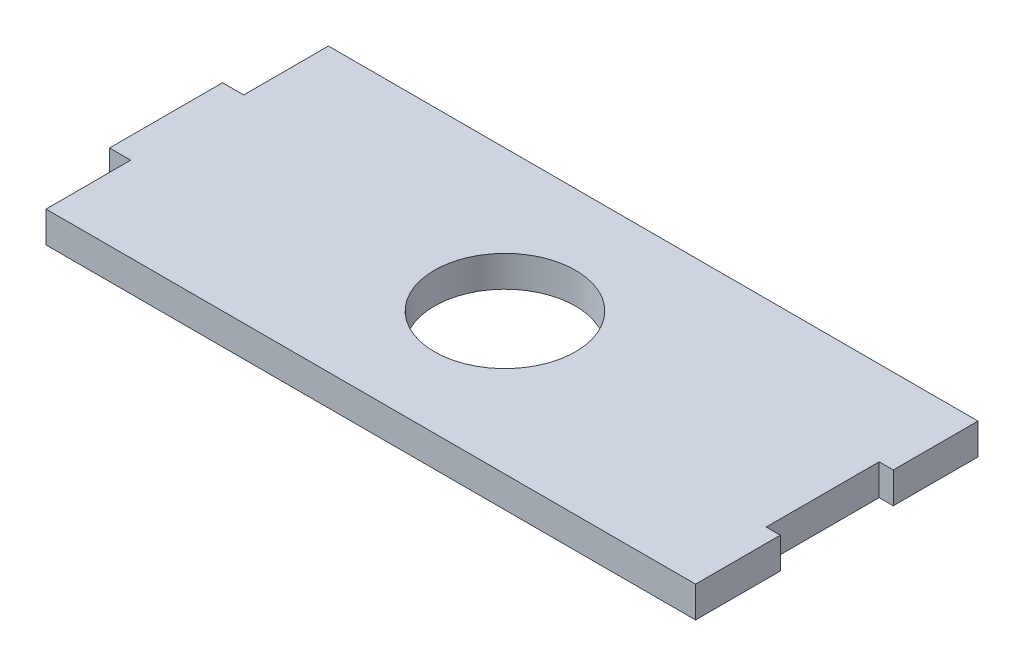
SolidWorks part; units mm, degrees
material "cardboard"
ref_plane "Front Plane" through (0, 0, 0) normal (0, 0, 1) x (1, 0, 0)
ref_plane "Top Plane" through (0, 0, 0) normal (0, 1, 0) x (1, 0, 0)
ref_plane "Right Plane" through (0, 0, 0) normal (1, 0, 0) x (0, 0, -1)
sketch "Sketch1" plane through (0, 0, 0) normal (0, 1, 0) x (1, 0, 0)
  line L0 (76.9454, 11.5977) -> (70.0953, 7.6428)
  line L1 (102.4454, -12.4023) -> (109.2956, -8.4474)
  line L2 (117.5953, 7.6428) -> (109.2956, 7.6428)
  line L3 (117.5953, -8.4474) -> (109.2956, -8.4474)
  line L4 (70.0953, 7.6428) -> (61.7956, 7.6428)
  line L5 (124.4454, 11.5977) -> (117.5953, 7.6428)
  line L6 (124.4454, -12.4023) -> (117.5953, -8.4474)
  line L7 (102.4454, 11.5977) -> (109.2956, 7.6428)
  line L8 (124.4454, 11.5977) -> (137.1954, 11.5977)
  line L9 (124.4454, -12.4023) -> (161.1954, -12.4023)
  line L10 (54.9454, 11.5977) -> (61.7956, 7.6428)
  line L11 (54.9454, -12.4023) -> (61.7956, -8.4474)
  line L12 (76.9454, -12.4023) -> (70.0953, -8.4474)
  line L13 (70.0953, -8.4474) -> (61.7956, -8.4474)
  line L14 (76.9454, 11.5977) -> (102.4454, 11.5977)
  line L15 (76.9454, -12.4023) -> (102.4454, -12.4023)
  line L16 (-12.8046, 77.3477) -> (-8.8496, 70.4976)
  line L17 (11.1954, 102.8477) -> (7.2405, 109.6979)
  line L18 (-8.8496, 117.9976) -> (-8.8496, 109.6979)
  line L19 (7.2405, 117.9976) -> (7.2405, 109.6979)
  line L20 (-8.8496, 70.4976) -> (-8.8496, 62.1979)
  line L21 (-12.8046, 124.8477) -> (-8.8496, 117.9976)
  line L22 (11.1954, 124.8477) -> (7.2405, 117.9976)
  line L23 (-12.8046, 102.8477) -> (-8.8496, 109.6979)
  line L24 (-12.8046, 124.8477) -> (-12.8046, 137.5977)
  line L25 (11.1954, 124.8477) -> (11.1954, 161.5977)
  line L26 (-12.8046, 55.3477) -> (-8.8496, 62.1979)
  line L27 (11.1954, 55.3477) -> (7.2405, 62.1979)
  line L28 (11.1954, 77.3477) -> (7.2405, 70.4976)
  line L29 (7.2405, 70.4976) -> (7.2405, 62.1979)
  line L30 (-12.8046, 77.3477) -> (-12.8046, 102.8477)
  line L31 (11.1954, 77.3477) -> (11.1954, 102.8477)
  line L32 (89.6954, 36.5977) -> (89.6954, 16.5977)
  line L33 (88.6954, 36.5977) -> (88.6954, 30.5977)
  line L34 (36.1954, 11.5977) -> (42.1954, 11.5977)
  line L35 (88.6954, 30.5977) -> (90.6954, 30.5977)
  line L36 (40.9454, 11.5977) -> (40.9454, 9.5977)
  line L37 (42.1954, 11.5977) -> (54.9454, 11.5977)
  line L38 (137.1954, 11.5977) -> (137.1954, -12.4023)
  line L39 (137.1954, 11.5977) -> (161.1954, 11.5977)
  line L40 (161.1954, 11.5977) -> (161.1954, 9.5977)
  line L41 (-29.301, 13.952) -> (-0.8046, -14.5444)
  line L42 (-29.301, 13.952) -> (-15.1588, 28.0941)
  line L43 (-0.8046, -14.5444) -> (13.3376, -0.4023)
  line L44 (-15.1588, 28.0941) -> (13.3376, -0.4023)
  line L45 (137.1954, 11.5977) -> (137.1954, 36.5977)
  line L46 (39.1954, 36.5977) -> (161.1954, 36.5977)
  line L47 (161.1954, 36.5977) -> (161.1954, 11.5977)
  line L48 (90.6954, 30.5977) -> (90.6954, 22.5977)
  line L49 (137.1954, 36.5977) -> (137.1954, 60.5977)
  line L50 (137.1954, 60.5977) -> (146.1954, 60.5977)
  line L51 (42.1954, 36.5977) -> (42.1954, 16.5977)
  line L52 (161.1954, 60.5977) -> (161.1954, 50.9197)
  line L53 (146.1954, 60.5977) -> (146.1954, 62.7977)
  line L54 (152.1954, 62.7977) -> (152.1954, 60.5977)
  line L55 (152.1954, 60.5977) -> (161.1954, 60.5977)
  line L56 (-59.8046, 137.5977) -> (-59.8046, 113.0977)
  line L57 (-39.8046, 113.0977) -> (-39.8046, 137.5977)
  line L58 (90.6954, 22.5977) -> (88.6954, 22.5977)
  line L59 (137.1954, -12.4023) -> (137.1954, -37.4023)
  line L60 (146.1954, -37.4023) -> (152.1954, -37.4023)
  line L61 (161.1954, -37.4023) -> (161.1954, -12.4023)
  line L62 (42.1954, -37.4023) -> (42.1954, -17.4023)
  line L63 (137.1954, -37.4023) -> (137.1954, -38.5823)
  line L64 (152.1954, -38.5823) -> (161.1954, -38.5823)
  line L65 (161.1954, -38.5823) -> (161.1954, -37.4023)
  line L66 (146.1954, -38.5823) -> (146.1954, -37.4023)
  line L67 (152.1954, -38.5823) -> (152.1954, -37.4023)
  line L68 (-38.9846, -138.4023) -> (-38.9846, -147.4023)
  line L69 (88.6954, 22.5977) -> (88.6954, 16.5977)
  line L70 (88.6954, 11.5977) -> (88.6954, 3.5977)
  line L71 (42.1954, -12.4023) -> (54.9454, -12.4023)
  line L72 (36.1954, -12.4023) -> (42.1954, -12.4023)
  line L73 (89.6692, 11.5977) -> (89.6692, -12.4023)
  line L74 (88.6954, 3.5977) -> (90.6954, 3.5977)
  line L75 (90.6954, 3.5977) -> (90.6954, -4.4023)
  line L76 (90.6954, -4.4023) -> (88.6954, -4.4023)
  line L77 (135.1954, 11.5977) -> (135.1954, 3.5977)
  line L78 (135.1954, 3.5977) -> (139.1954, 3.5977)
  line L79 (37.3754, 161.5977) -> (37.3754, 152.5977)
  line L80 (37.1954, 34.5977) -> (37.1954, 18.5977)
  line L81 (39.1954, 16.5977) -> (137.1954, 16.5977)
  line L82 (40.9454, 23.5977) -> (40.9454, 16.5977)
  line L83 (42.1954, 29.5977) -> (39.1954, 29.5977)
  line L84 (39.1954, 29.5977) -> (39.1954, 23.5977)
  line L85 (43.4454, 5.5977) -> (40.9454, 5.5977)
  line L86 (5.1954, -42.1523) -> (5.1954, -40.1523)
  line L87 (40.9454, -6.4023) -> (43.4454, -6.4023)
  line L88 (43.4454, 5.5977) -> (43.4454, -6.4023)
  line L89 (42.1954, 11.5977) -> (42.1954, 5.5977)
  line L90 (40.9454, 9.5977) -> (43.4454, 9.5977)
  line L91 (43.4454, 9.5977) -> (43.4454, 7.5977)
  line L92 (43.4454, 7.5977) -> (40.9454, 7.5977)
  line L93 (40.9454, 7.5977) -> (40.9454, 5.5977)
  line L94 (40.9454, -8.4023) -> (40.9454, -6.4023)
  line L95 (43.4454, -8.4023) -> (40.9454, -8.4023)
  line L96 (43.4454, -10.4023) -> (43.4454, -8.4023)
  line L97 (40.9454, -10.4023) -> (43.4454, -10.4023)
  line L98 (40.9454, -12.4023) -> (40.9454, -10.4023)
  line L99 (139.1954, 3.5977) -> (139.1954, -4.4023)
  line L100 (139.1954, -4.4023) -> (135.1954, -4.4023)
  line L101 (135.1954, -4.4023) -> (135.1954, -12.4023)
  line L102 (137.1954, 13.5977) -> (145.1954, 13.5977)
  line L103 (145.1954, 13.5977) -> (145.1954, 9.5977)
  line L104 (145.1954, 9.5977) -> (153.1954, 9.5977)
  line L105 (153.1954, 9.5977) -> (153.1954, 13.5977)
  line L106 (153.1954, 13.5977) -> (161.1954, 13.5977)
  line L107 (135.6954, 36.5977) -> (135.6954, 30.5977)
  line L108 (135.6954, 30.5977) -> (138.6954, 30.5977)
  line L109 (138.6954, 30.5977) -> (138.6954, 22.5977)
  line L110 (138.6954, 22.5977) -> (135.6954, 22.5977)
  line L111 (135.6954, 22.5977) -> (135.6954, 16.5977)
  line L112 (88.6954, -4.4023) -> (88.6954, -12.4023)
  line L113 (88.6954, -23.4023) -> (88.6954, -17.4023)
  line L114 (89.6954, -37.4023) -> (89.6954, -17.4023)
  line L115 (90.6954, -23.4023) -> (88.6954, -23.4023)
  line L116 (90.6954, -31.4023) -> (90.6954, -23.4023)
  line L117 (153.1954, -14.4023) -> (161.1954, -14.4023)
  line L118 (153.1954, -10.4023) -> (153.1954, -14.4023)
  line L119 (145.1954, -10.4023) -> (153.1954, -10.4023)
  line L120 (145.1954, -14.4023) -> (145.1954, -10.4023)
  line L121 (137.1954, -14.4023) -> (145.1954, -14.4023)
  line L122 (135.6954, -23.4023) -> (135.6954, -17.4023)
  line L123 (138.6954, -23.4023) -> (135.6954, -23.4023)
  line L124 (40.9454, 36.5977) -> (40.9454, 29.5977)
  line L125 (42.1954, 23.5977) -> (39.1954, 23.5977)
  line L126 (137.1954, -37.4023) -> (39.1954, -37.4023)
  line L127 (37.1954, -35.4023) -> (37.1954, -19.4023)
  line L128 (39.1954, -17.4023) -> (137.1954, -17.4023)
  line L129 (138.6954, -31.4023) -> (138.6954, -23.4023)
  line L130 (135.6954, -31.4023) -> (138.6954, -31.4023)
  line L131 (135.6954, -37.4023) -> (135.6954, -31.4023)
  line L132 (88.6954, -31.4023) -> (90.6954, -31.4023)
  line L133 (88.6954, -37.4023) -> (88.6954, -31.4023)
  line L134 (137.1954, 38.5977) -> (145.1954, 38.5977)
  line L135 (145.1954, 38.5977) -> (145.1954, 34.5977)
  line L136 (145.1954, 34.5977) -> (153.1954, 34.5977)
  line L137 (153.1954, 34.5977) -> (153.1954, 38.5977)
  line L138 (153.1954, 38.5977) -> (161.1954, 38.5977)
  line L139 (-45.3046, 133.3477) -> (-45.3046, 117.3477)
  line L140 (-56.8046, 133.3477) -> (-54.3046, 133.3477)
  line L141 (-56.8046, 133.3477) -> (-56.8046, 117.3477)
  line L142 (-56.8046, 117.3477) -> (-54.3046, 117.3477)
  line L143 (-54.3046, 133.3477) -> (-54.3046, 117.3477)
  line L144 (40.9454, -24.4023) -> (40.9454, -17.4023)
  line L145 (42.1954, -24.4023) -> (39.1954, -24.4023)
  line L146 (39.1954, -30.4023) -> (39.1954, -24.4023)
  line L147 (42.1954, -30.4023) -> (39.1954, -30.4023)
  line L148 (40.9454, -37.4023) -> (40.9454, -30.4023)
  line L149 (196.1954, 4.5977) -> (196.1954, -5.4023)
  line L150 (191.1954, 9.5977) -> (161.1954, 9.5977)
  line L151 (191.1954, -10.4023) -> (161.1954, -10.4023)
  line L152 (191.1954, 9.5977) -> (196.1954, 4.5977)
  line L153 (196.1954, -5.4023) -> (191.1954, -10.4023)
  line L154 (161.1954, -10.4023) -> (161.1954, -12.4023)
  line L155 (137.1954, 62.7977) -> (146.1954, 62.7977)
  line L156 (137.1954, 62.7977) -> (137.1954, 64.7977)
  line L157 (137.1954, 64.7977) -> (161.1954, 64.7977)
  line L158 (161.1954, 64.7977) -> (161.1954, 62.7977)
  line L159 (152.1954, 62.7977) -> (161.1954, 62.7977)
  line L160 (-42.8046, 117.3477) -> (-45.3046, 117.3477)
  line L161 (-42.8046, 133.3477) -> (-42.8046, 117.3477)
  line L162 (-42.8046, 133.3477) -> (-45.3046, 133.3477)
  line L163 (154.5954, 50.9197) -> (161.1954, 50.9197)
  line L164 (154.5954, 50.9197) -> (154.5954, 46.4197)
  line L165 (154.5954, 46.4197) -> (161.1954, 46.4197)
  line L166 (161.1954, 46.4197) -> (161.1954, 36.5977)
  line L167 (11.1954, -78.1523) -> (7.2405, -71.3021)
  line L168 (-12.8046, -103.6523) -> (-8.8496, -110.5024)
  line L169 (7.2405, -118.8021) -> (7.2405, -110.5024)
  line L170 (11.1954, -37.4023) -> (11.1954, -43.4023)
  line L171 (11.1954, -42.1523) -> (9.1954, -42.1523)
  line L172 (11.1954, -43.4023) -> (11.1954, -56.1523)
  line L173 (-8.8496, -118.8021) -> (-8.8496, -110.5024)
  line L174 (7.2405, -71.3021) -> (7.2405, -63.0024)
  line L175 (11.1954, -125.6523) -> (7.2405, -118.8021)
  line L176 (-12.8046, -125.6523) -> (-8.8496, -118.8021)
  line L177 (11.1954, -103.6523) -> (7.2405, -110.5024)
  line L178 (11.1954, -125.6523) -> (11.1954, -138.4023)
  line L179 (-12.8046, -125.6523) -> (-12.8046, -162.4023)
  line L180 (11.1954, -56.1523) -> (7.2405, -63.0024)
  line L181 (-12.8046, -56.1523) -> (-8.8496, -63.0024)
  line L182 (36.1954, -43.4023) -> (16.1954, -43.4023)
  line L183 (-12.8046, -78.1523) -> (-8.8496, -71.3021)
  line L184 (-8.8496, -71.3021) -> (-8.8496, -63.0024)
  line L185 (11.1954, -78.1523) -> (11.1954, -103.6523)
  line L186 (-12.8046, -78.1523) -> (-12.8046, -103.6523)
  line L187 (36.1954, -90.9023) -> (16.1954, -90.9023)
  line L188 (36.1954, -89.9023) -> (30.1954, -89.9023)
  line L189 (30.1954, -89.9023) -> (30.1954, -91.9023)
  line L190 (11.1954, -138.4023) -> (-12.8046, -138.4023)
  line L191 (11.1954, -138.4023) -> (11.1954, -162.4023)
  line L192 (11.1954, -162.4023) -> (9.1954, -162.4023)
  line L193 (11.1954, -138.4023) -> (36.1954, -138.4023)
  line L194 (36.1954, -40.4023) -> (36.1954, -162.4023)
  line L195 (-37.8046, -43.4023) -> (-17.8046, -43.4023)
  line L196 (36.1954, -162.4023) -> (11.1954, -162.4023)
  line L197 (30.1954, -91.9023) -> (22.1954, -91.9023)
  line L198 (36.1954, -138.4023) -> (60.1954, -138.4023)
  line L199 (60.1954, -138.4023) -> (60.1954, -147.4023)
  line L200 (60.1954, -162.4023) -> (50.5174, -162.4023)
  line L201 (60.1954, -147.4023) -> (62.3954, -147.4023)
  line L202 (62.3954, -153.4023) -> (60.1954, -153.4023)
  line L203 (60.1954, -153.4023) -> (60.1954, -162.4023)
  line L204 (-12.8046, -43.4023) -> (-12.8046, -56.1523)
  line L205 (-12.8046, -37.4023) -> (-12.8046, -43.4023)
  line L206 (22.1954, -91.9023) -> (22.1954, -89.9023)
  line L207 (-12.8046, -138.4023) -> (-37.8046, -138.4023)
  line L208 (-37.8046, -147.4023) -> (-37.8046, -153.4023)
  line L209 (37.3754, 146.5977) -> (37.3754, 137.5977)
  line L210 (34.1954, -38.4023) -> (18.1954, -38.4023)
  line L211 (16.1954, -40.4023) -> (16.1954, -138.4023)
  line L212 (23.1954, -42.1523) -> (16.1954, -42.1523)
  line L213 (29.1954, -43.4023) -> (29.1954, -40.4023)
  line L214 (29.1954, -40.4023) -> (23.1954, -40.4023)
  line L215 (5.1954, -44.6523) -> (5.1954, -42.1523)
  line L216 (-37.8046, -162.4023) -> (-12.8046, -162.4023)
  line L217 (-6.8046, -42.1523) -> (-6.8046, -44.6523)
  line L218 (5.1954, -44.6523) -> (-6.8046, -44.6523)
  line L219 (11.1954, -43.4023) -> (5.1954, -43.4023)
  line L220 (9.1954, -42.1523) -> (9.1954, -44.6523)
  line L221 (9.1954, -44.6523) -> (7.1954, -44.6523)
  line L222 (7.1954, -44.6523) -> (7.1954, -42.1523)
  line L223 (7.1954, -42.1523) -> (5.1954, -42.1523)
  line L224 (-8.8046, -42.1523) -> (-6.8046, -42.1523)
  line L225 (-8.8046, -44.6523) -> (-8.8046, -42.1523)
  line L226 (-10.8046, -44.6523) -> (-8.8046, -44.6523)
  line L227 (-10.8046, -42.1523) -> (-10.8046, -44.6523)
  line L228 (-12.8046, -42.1523) -> (-10.8046, -42.1523)
  line L229 (-37.8046, -138.4023) -> (-38.9846, -138.4023)
  line L230 (-38.9846, -153.4023) -> (-38.9846, -162.4023)
  line L231 (-38.9846, -162.4023) -> (-37.8046, -162.4023)
  line L232 (-38.9846, -147.4023) -> (-37.8046, -147.4023)
  line L233 (-38.9846, -153.4023) -> (-37.8046, -153.4023)
  line L234 (-162.8046, 37.7777) -> (-153.8046, 37.7777)
  line L235 (22.1954, -89.9023) -> (16.1954, -89.9023)
  line L236 (11.1954, -89.9023) -> (3.1954, -89.9023)
  line L237 (11.1954, -90.8761) -> (-12.8046, -90.8761)
  line L238 (3.1954, -89.9023) -> (3.1954, -91.9023)
  line L239 (3.1954, -91.9023) -> (-4.8046, -91.9023)
  line L240 (-4.8046, -91.9023) -> (-4.8046, -89.9023)
  line L241 (11.1954, -136.4023) -> (3.1954, -136.4023)
  line L242 (3.1954, -136.4023) -> (3.1954, -140.4023)
  line L243 (3.1954, -140.4023) -> (-4.8046, -140.4023)
  line L244 (-4.8046, -140.4023) -> (-4.8046, -136.4023)
  line L245 (-4.8046, -136.4023) -> (-12.8046, -136.4023)
  line L246 (13.1954, -138.4023) -> (13.1954, -146.4023)
  line L247 (13.1954, -146.4023) -> (9.1954, -146.4023)
  line L248 (9.1954, -146.4023) -> (9.1954, -154.4023)
  line L249 (9.1954, -154.4023) -> (13.1954, -154.4023)
  line L250 (13.1954, -154.4023) -> (13.1954, -162.4023)
  line L251 (36.1954, -136.9023) -> (30.1954, -136.9023)
  line L252 (30.1954, -136.9023) -> (30.1954, -139.9023)
  line L253 (30.1954, -139.9023) -> (22.1954, -139.9023)
  line L254 (36.1954, -42.1523) -> (29.1954, -42.1523)
  line L255 (23.1954, -43.4023) -> (23.1954, -40.4023)
  line L256 (-37.8046, -138.4023) -> (-37.8046, -40.4023)
  line L257 (-35.8046, -38.4023) -> (-19.8046, -38.4023)
  line L258 (-17.8046, -40.4023) -> (-17.8046, -138.4023)
  line L259 (22.1954, -139.9023) -> (22.1954, -136.9023)
  line L260 (22.1954, -136.9023) -> (16.1954, -136.9023)
  line L261 (-4.8046, -89.9023) -> (-12.8046, -89.9023)
  line L262 (-23.8046, -89.9023) -> (-17.8046, -89.9023)
  line L263 (-37.8046, -90.9023) -> (-17.8046, -90.9023)
  line L264 (-23.8046, -91.9023) -> (-23.8046, -89.9023)
  line L265 (-31.8046, -91.9023) -> (-23.8046, -91.9023)
  line L266 (-14.8046, -154.4023) -> (-14.8046, -162.4023)
  line L267 (-10.8046, -154.4023) -> (-14.8046, -154.4023)
  line L268 (-10.8046, -146.4023) -> (-10.8046, -154.4023)
  line L269 (-14.8046, -146.4023) -> (-10.8046, -146.4023)
  line L270 (-14.8046, -138.4023) -> (-14.8046, -146.4023)
  line L271 (-23.8046, -136.9023) -> (-17.8046, -136.9023)
  line L272 (-23.8046, -139.9023) -> (-23.8046, -136.9023)
  line L273 (-31.8046, -139.9023) -> (-23.8046, -139.9023)
  line L274 (-24.8046, -42.1523) -> (-17.8046, -42.1523)
  line L275 (-24.8046, -43.4023) -> (-24.8046, -40.4023)
  line L276 (-30.8046, -40.4023) -> (-24.8046, -40.4023)
  line L277 (-30.8046, -43.4023) -> (-30.8046, -40.4023)
  line L278 (-37.8046, -42.1523) -> (-30.8046, -42.1523)
  line L279 (-31.8046, -136.9023) -> (-31.8046, -139.9023)
  line L280 (-37.8046, -136.9023) -> (-31.8046, -136.9023)
  line L281 (-31.8046, -89.9023) -> (-31.8046, -91.9023)
  line L282 (-37.8046, -89.9023) -> (-31.8046, -89.9023)
  line L283 (38.1954, -138.4023) -> (38.1954, -146.4023)
  line L284 (38.1954, -146.4023) -> (34.1954, -146.4023)
  line L285 (34.1954, -146.4023) -> (34.1954, -154.4023)
  line L286 (34.1954, -154.4023) -> (38.1954, -154.4023)
  line L287 (38.1954, -154.4023) -> (38.1954, -162.4023)
  line L288 (4.1954, -197.4023) -> (-5.8046, -197.4023)
  line L289 (9.1954, -192.4023) -> (9.1954, -162.4023)
  line L290 (-10.8046, -192.4023) -> (-10.8046, -162.4023)
  line L291 (9.1954, -192.4023) -> (4.1954, -197.4023)
  line L292 (-5.8046, -197.4023) -> (-10.8046, -192.4023)
  line L293 (-10.8046, -162.4023) -> (-12.8046, -162.4023)
  line L294 (62.3954, -138.4023) -> (62.3954, -147.4023)
  line L295 (62.3954, -138.4023) -> (64.3954, -138.4023)
  line L296 (64.3954, -138.4023) -> (64.3954, -162.4023)
  line L297 (64.3954, -162.4023) -> (62.3954, -162.4023)
  line L298 (62.3954, -153.4023) -> (62.3954, -162.4023)
  line L299 (-37.8046, -12.4023) -> (-43.8046, -12.4023)
  line L300 (-42.5546, -12.4023) -> (-42.5546, -10.4023)
  line L301 (-43.8046, -12.4023) -> (-56.5546, -12.4023)
  line L302 (50.5174, -155.8023) -> (50.5174, -162.4023)
  line L303 (50.5174, -155.8023) -> (46.0174, -155.8023)
  line L304 (-43.8046, -37.4023) -> (-43.8046, -17.4023)
  line L305 (46.0174, -155.8023) -> (46.0174, -162.4023)
  line L306 (46.0174, -162.4023) -> (36.1954, -162.4023)
  line L307 (-78.5546, -12.4023) -> (-71.7044, -8.4474)
  line L308 (-104.0546, 11.5977) -> (-110.9047, 7.6428)
  line L309 (-119.2044, -8.4474) -> (-110.9047, -8.4474)
  line L310 (-119.2044, 7.6428) -> (-110.9047, 7.6428)
  line L311 (-71.7044, -8.4474) -> (-63.4047, -8.4474)
  line L312 (-126.0546, -12.4023) -> (-119.2044, -8.4474)
  line L313 (-126.0546, 11.5977) -> (-119.2044, 7.6428)
  line L314 (-104.0546, -12.4023) -> (-110.9047, -8.4474)
  line L315 (-126.0546, -12.4023) -> (-138.8046, -12.4023)
  line L316 (-43.8046, 36.5977) -> (-43.8046, 16.5977)
  line L317 (-126.0546, 11.5977) -> (-162.8046, 11.5977)
  line L318 (-56.5546, -12.4023) -> (-63.4047, -8.4474)
  line L319 (-56.5546, 11.5977) -> (-63.4047, 7.6428)
  line L320 (-78.5546, 11.5977) -> (-71.7044, 7.6428)
  line L321 (-71.7044, 7.6428) -> (-63.4047, 7.6428)
  line L322 (-78.5546, -12.4023) -> (-104.0546, -12.4023)
  line L323 (-78.5546, 11.5977) -> (-104.0546, 11.5977)
  line L324 (-91.3046, -37.4023) -> (-91.3046, -17.4023)
  line L325 (-43.8046, 11.5977) -> (-56.5546, 11.5977)
  line L326 (-37.8046, 11.5977) -> (-43.8046, 11.5977)
  line L327 (-90.3046, -37.4023) -> (-90.3046, -31.4023)
  line L328 (-90.3046, -31.4023) -> (-92.3046, -31.4023)
  line L329 (-138.8046, -12.4023) -> (-138.8046, 11.5977)
  line L330 (-138.8046, -12.4023) -> (-162.8046, -12.4023)
  line L331 (-162.8046, -12.4023) -> (-162.8046, -10.4023)
  line L332 (-138.8046, -12.4023) -> (-138.8046, -37.4023)
  line L333 (137.1954, -38.5823) -> (146.1954, -38.5823)
  line L334 (-38.8046, -35.4023) -> (-38.8046, -19.4023)
  line L335 (-40.8046, -17.4023) -> (-138.8046, -17.4023)
  line L336 (-42.5546, -24.4023) -> (-42.5546, -17.4023)
  line L337 (-43.8046, -30.4023) -> (-40.8046, -30.4023)
  line L338 (-40.8046, -30.4023) -> (-40.8046, -24.4023)
  line L339 (-45.0546, -6.4023) -> (-42.5546, -6.4023)
  line L340 (-40.8046, -37.4023) -> (-162.8046, -37.4023)
  line L341 (-42.5546, 5.5977) -> (-45.0546, 5.5977)
  line L342 (-45.0546, -6.4023) -> (-45.0546, 5.5977)
  line L343 (-43.8046, -12.4023) -> (-43.8046, -6.4023)
  line L344 (-42.5546, -10.4023) -> (-45.0546, -10.4023)
  line L345 (-45.0546, -10.4023) -> (-45.0546, -8.4023)
  line L346 (-45.0546, -8.4023) -> (-42.5546, -8.4023)
  line L347 (-42.5546, -8.4023) -> (-42.5546, -6.4023)
  line L348 (-42.5546, 7.5977) -> (-42.5546, 5.5977)
  line L349 (-45.0546, 7.5977) -> (-42.5546, 7.5977)
  line L350 (-45.0546, 9.5977) -> (-45.0546, 7.5977)
  line L351 (-42.5546, 9.5977) -> (-45.0546, 9.5977)
  line L352 (-42.5546, 11.5977) -> (-42.5546, 9.5977)
  line L353 (-162.8046, -37.4023) -> (-162.8046, -12.4023)
  line L354 (-92.3046, -31.4023) -> (-92.3046, -23.4023)
  line L355 (-138.8046, -37.4023) -> (-138.8046, -61.4023)
  line L356 (-138.8046, -61.4023) -> (-147.8046, -61.4023)
  line L357 (-162.8046, -61.4023) -> (-162.8046, -51.7243)
  line L358 (-147.8046, -61.4023) -> (-147.8046, -63.6023)
  line L359 (-153.8046, -63.6023) -> (-153.8046, -61.4023)
  line L360 (-153.8046, -61.4023) -> (-162.8046, -61.4023)
  line L361 (-92.3046, -23.4023) -> (-90.3046, -23.4023)
  line L362 (-138.8046, 11.5977) -> (-138.8046, 36.5977)
  line L363 (-147.8046, 36.5977) -> (-153.8046, 36.5977)
  line L364 (-162.8046, 36.5977) -> (-162.8046, 11.5977)
  line L365 (-138.8046, 36.5977) -> (-138.8046, 37.7777)
  line L366 (-162.8046, 37.7777) -> (-162.8046, 36.5977)
  line L367 (-147.8046, 37.7777) -> (-147.8046, 36.5977)
  line L368 (-153.8046, 37.7777) -> (-153.8046, 36.5977)
  line L369 (-147.8046, 37.7777) -> (-138.8046, 37.7777)
  line L370 (-90.3046, -23.4023) -> (-90.3046, -17.4023)
  line L371 (-90.3046, -12.4023) -> (-90.3046, -4.4023)
  line L372 (-91.2784, -12.4023) -> (-91.2784, 11.5977)
  line L373 (-90.3046, -4.4023) -> (-92.3046, -4.4023)
  line L374 (-42.5546, -37.4023) -> (-42.5546, -30.4023)
  line L375 (-43.8046, -24.4023) -> (-40.8046, -24.4023)
  line L376 (-138.8046, 36.5977) -> (-40.8046, 36.5977)
  line L377 (-38.8046, 34.5977) -> (-38.8046, 18.5977)
  line L378 (-40.8046, 16.5977) -> (-138.8046, 16.5977)
  line L379 (-92.3046, -4.4023) -> (-92.3046, 3.5977)
  line L380 (-92.3046, 3.5977) -> (-90.3046, 3.5977)
  line L381 (-136.8046, -12.4023) -> (-136.8046, -4.4023)
  line L382 (-136.8046, -4.4023) -> (-140.8046, -4.4023)
  line L383 (-140.8046, -4.4023) -> (-140.8046, 3.5977)
  line L384 (-140.8046, 3.5977) -> (-136.8046, 3.5977)
  line L385 (-136.8046, 3.5977) -> (-136.8046, 11.5977)
  line L386 (-138.8046, -14.4023) -> (-146.8046, -14.4023)
  line L387 (-146.8046, -14.4023) -> (-146.8046, -10.4023)
  line L388 (-146.8046, -10.4023) -> (-154.8046, -10.4023)
  line L389 (-154.8046, -10.4023) -> (-154.8046, -14.4023)
  line L390 (-154.8046, -14.4023) -> (-162.8046, -14.4023)
  line L391 (-137.3046, -37.4023) -> (-137.3046, -31.4023)
  line L392 (-37.8046, 90.0977) -> (-17.8046, 90.0977)
  line L393 (-37.8046, 89.0977) -> (-31.8046, 89.0977)
  line L394 (-42.5546, 23.5977) -> (-42.5546, 16.5977)
  line L395 (-43.8046, 23.5977) -> (-40.8046, 23.5977)
  line L396 (-40.8046, 29.5977) -> (-40.8046, 23.5977)
  line L397 (-43.8046, 29.5977) -> (-40.8046, 29.5977)
  line L398 (-42.5546, 36.5977) -> (-42.5546, 29.5977)
  line L399 (-137.3046, -31.4023) -> (-140.3046, -31.4023)
  line L400 (-140.3046, -31.4023) -> (-140.3046, -23.4023)
  line L401 (-140.3046, -23.4023) -> (-137.3046, -23.4023)
  line L402 (-137.3046, -23.4023) -> (-137.3046, -17.4023)
  line L403 (-90.3046, 3.5977) -> (-90.3046, 11.5977)
  line L404 (-90.3046, 22.5977) -> (-90.3046, 16.5977)
  line L405 (-91.3046, 36.5977) -> (-91.3046, 16.5977)
  line L406 (-92.3046, 22.5977) -> (-90.3046, 22.5977)
  line L407 (-92.3046, 30.5977) -> (-92.3046, 22.5977)
  line L408 (-154.8046, 13.5977) -> (-162.8046, 13.5977)
  line L409 (-154.8046, 9.5977) -> (-154.8046, 13.5977)
  line L410 (-146.8046, 9.5977) -> (-154.8046, 9.5977)
  line L411 (-146.8046, 13.5977) -> (-146.8046, 9.5977)
  line L412 (-138.8046, 13.5977) -> (-146.8046, 13.5977)
  line L413 (-137.3046, 22.5977) -> (-137.3046, 16.5977)
  line L414 (-140.3046, 22.5977) -> (-137.3046, 22.5977)
  line L415 (-140.3046, 30.5977) -> (-140.3046, 22.5977)
  line L416 (-137.3046, 30.5977) -> (-140.3046, 30.5977)
  line L417 (-137.3046, 36.5977) -> (-137.3046, 30.5977)
  line L418 (-90.3046, 30.5977) -> (-92.3046, 30.5977)
  line L419 (-90.3046, 36.5977) -> (-90.3046, 30.5977)
  line L420 (-138.8046, -39.4023) -> (-146.8046, -39.4023)
  line L421 (-146.8046, -39.4023) -> (-146.8046, -35.4023)
  line L422 (-146.8046, -35.4023) -> (-154.8046, -35.4023)
  line L423 (-154.8046, -35.4023) -> (-154.8046, -39.4023)
  line L424 (-154.8046, -39.4023) -> (-162.8046, -39.4023)
  line L425 (-12.8046, 41.3477) -> (-10.8046, 41.3477)
  line L426 (-31.8046, 89.0977) -> (-31.8046, 91.0977)
  line L427 (-12.8046, 137.5977) -> (11.1954, 137.5977)
  line L428 (-12.8046, 137.5977) -> (-12.8046, 161.5977)
  line L429 (-12.8046, 161.5977) -> (-10.8046, 161.5977)
  line L430 (-12.8046, 137.5977) -> (-37.8046, 137.5977)
  line L431 (-37.8046, 137.5977) -> (-37.8046, 161.5977)
  line L432 (-37.8046, 161.5977) -> (-12.8046, 161.5977)
  line L433 (-37.8046, 137.5977) -> (-37.8046, 42.5977)
  line L434 (-37.8046, 42.5977) -> (-17.8046, 42.5977)
  line L435 (-17.8046, 42.5977) -> (-17.8046, 137.5977)
  line L436 (-31.8046, 91.0977) -> (-23.8046, 91.0977)
  line L437 (-37.8046, 137.5977) -> (-61.8046, 137.5977)
  line L438 (-61.8046, 137.5977) -> (-61.8046, 146.5977)
  line L439 (-61.8046, 161.5977) -> (-52.1265, 161.5977)
  line L440 (-61.8046, 146.5977) -> (-64.0046, 146.5977)
  line L441 (-64.0046, 152.5977) -> (-61.8046, 152.5977)
  line L442 (-61.8046, 152.5977) -> (-61.8046, 161.5977)
  line L443 (-59.8046, 113.0977) -> (-39.8046, 113.0977)
  line L444 (36.1954, 42.5977) -> (16.1954, 42.5977)
  line L445 (-23.8046, 91.0977) -> (-23.8046, 89.0977)
  line L446 (36.1954, 137.5977) -> (36.1954, 42.5977)
  line L447 (16.1954, 42.5977) -> (16.1954, 137.5977)
  line L448 (11.1954, 137.5977) -> (36.1954, 137.5977)
  line L449 (36.1954, 146.5977) -> (36.1954, 152.5977)
  line L450 (36.1954, 161.5977) -> (11.1954, 161.5977)
  line L451 (11.1954, 36.5977) -> (11.1954, 55.3477)
  line L452 (36.1954, 137.5977) -> (37.3754, 137.5977)
  line L453 (37.3754, 161.5977) -> (36.1954, 161.5977)
  line L454 (37.3754, 146.5977) -> (36.1954, 146.5977)
  line L455 (37.3754, 152.5977) -> (36.1954, 152.5977)
  line L456 (-37.8046, 42.5977) -> (-37.8046, 39.5977)
  line L457 (-35.8046, 37.5977) -> (-19.8046, 37.5977)
  line L458 (-17.8046, 39.5977) -> (-17.8046, 42.5977)
  line L459 (34.1954, 37.5977) -> (18.1954, 37.5977)
  line L460 (16.1954, 39.5977) -> (16.1954, 42.5977)
  line L461 (-6.8046, 43.8477) -> (-6.8046, 41.3477)
  line L462 (-23.8046, 89.0977) -> (-17.8046, 89.0977)
  line L463 (5.1954, 41.3477) -> (5.1954, 43.8477)
  line L464 (-6.8046, 43.8477) -> (5.1954, 43.8477)
  line L465 (-12.8046, 42.5977) -> (-6.8046, 42.5977)
  line L466 (-10.8046, 41.3477) -> (-10.8046, 43.8477)
  line L467 (-10.8046, 43.8477) -> (-8.8046, 43.8477)
  line L468 (-8.8046, 43.8477) -> (-8.8046, 41.3477)
  line L469 (-8.8046, 41.3477) -> (-6.8046, 41.3477)
  line L470 (7.1954, 41.3477) -> (5.1954, 41.3477)
  line L471 (7.1954, 43.8477) -> (7.1954, 41.3477)
  line L472 (9.1954, 43.8477) -> (7.1954, 43.8477)
  line L473 (9.1954, 41.3477) -> (9.1954, 43.8477)
  line L474 (11.1954, 41.3477) -> (9.1954, 41.3477)
  line L475 (-12.8046, 89.0977) -> (-4.8046, 89.0977)
  line L476 (-12.8046, 90.0715) -> (11.1954, 90.0715)
  line L477 (-4.8046, 89.0977) -> (-4.8046, 91.0977)
  line L478 (-4.8046, 91.0977) -> (3.1954, 91.0977)
  line L479 (3.1954, 91.0977) -> (3.1954, 89.0977)
  line L480 (-12.8046, 135.5977) -> (-4.8046, 135.5977)
  line L481 (-4.8046, 135.5977) -> (-4.8046, 139.5977)
  line L482 (-4.8046, 139.5977) -> (3.1954, 139.5977)
  line L483 (3.1954, 139.5977) -> (3.1954, 135.5977)
  line L484 (3.1954, 135.5977) -> (11.1954, 135.5977)
  line L485 (-14.8046, 137.5977) -> (-14.8046, 145.5977)
  line L486 (-14.8046, 145.5977) -> (-10.8046, 145.5977)
  line L487 (-10.8046, 145.5977) -> (-10.8046, 153.5977)
  line L488 (-10.8046, 153.5977) -> (-14.8046, 153.5977)
  line L489 (-14.8046, 153.5977) -> (-14.8046, 161.5977)
  line L490 (-37.8046, 136.0977) -> (-31.8046, 136.0977)
  line L491 (-31.8046, 136.0977) -> (-31.8046, 139.0977)
  line L492 (-31.8046, 139.0977) -> (-23.8046, 139.0977)
  line L493 (-23.8046, 139.0977) -> (-23.8046, 136.0977)
  line L494 (-23.8046, 136.0977) -> (-17.8046, 136.0977)
  line L495 (3.1954, 89.0977) -> (11.1954, 89.0977)
  line L496 (22.1954, 89.0977) -> (16.1954, 89.0977)
  line L497 (36.1954, 90.0977) -> (16.1954, 90.0977)
  line L498 (22.1954, 91.0977) -> (22.1954, 89.0977)
  line L499 (30.1954, 91.0977) -> (22.1954, 91.0977)
  line L500 (-37.8046, 41.3477) -> (-30.8046, 41.3477)
  line L501 (29.1954, 39.5977) -> (23.1954, 39.5977)
  line L502 (23.1954, 41.3477) -> (16.1954, 41.3477)
  line L503 (-30.8046, 42.5977) -> (-30.8046, 39.5977)
  line L504 (-24.8046, 41.3477) -> (-17.8046, 41.3477)
  line L505 (13.1954, 153.5977) -> (13.1954, 161.5977)
  line L506 (9.1954, 153.5977) -> (13.1954, 153.5977)
  line L507 (9.1954, 145.5977) -> (9.1954, 153.5977)
  line L508 (13.1954, 145.5977) -> (9.1954, 145.5977)
  line L509 (13.1954, 137.5977) -> (13.1954, 145.5977)
  line L510 (22.1954, 136.0977) -> (16.1954, 136.0977)
  line L511 (22.1954, 139.0977) -> (22.1954, 136.0977)
  line L512 (30.1954, 139.0977) -> (22.1954, 139.0977)
  line L513 (30.1954, 136.0977) -> (30.1954, 139.0977)
  line L514 (36.1954, 136.0977) -> (30.1954, 136.0977)
  line L515 (30.1954, 89.0977) -> (30.1954, 91.0977)
  line L516 (36.1954, 89.0977) -> (30.1954, 89.0977)
  line L517 (11.1954, 36.5977) -> (20.1599, 27.6332)
  line L518 (36.1954, -12.4023) -> (27.231, -21.3668)
  line L519 (-12.8046, -37.4023) -> (-21.769, -28.4378)
  line L520 (23.1954, 42.5977) -> (23.1954, 39.5977)
  line L521 (-24.8046, 42.5977) -> (-24.8046, 39.5977)
  line L522 (29.1954, 42.5977) -> (29.1954, 39.5977)
  line L523 (36.1954, 41.3477) -> (29.1954, 41.3477)
  line L524 (-39.8046, 137.5977) -> (-39.8046, 145.5977)
  line L525 (-39.8046, 145.5977) -> (-35.8046, 145.5977)
  line L526 (-35.8046, 145.5977) -> (-35.8046, 153.5977)
  line L527 (-35.8046, 153.5977) -> (-39.8046, 153.5977)
  line L528 (-39.8046, 153.5977) -> (-39.8046, 161.5977)
  line L529 (-59.8046, 136.0977) -> (-52.8046, 136.0977)
  line L530 (-52.8046, 136.0977) -> (-52.8046, 139.0977)
  line L531 (-52.8046, 139.0977) -> (-46.8046, 139.0977)
  line L532 (-46.8046, 139.0977) -> (-46.8046, 136.0977)
  line L533 (-46.8046, 136.0977) -> (-39.8046, 136.0977)
  line L534 (-12.8046, 36.5977) -> (-12.8046, 55.3477)
  line L535 (42.1954, -6.4023) -> (42.1954, -12.4023)
  line L536 (5.1954, 42.5977) -> (11.1954, 42.5977)
  line L537 (-43.8046, 5.5977) -> (-43.8046, 11.5977)
  line L538 (-6.8046, -43.4023) -> (-12.8046, -43.4023)
  line L539 (-5.8046, 196.5977) -> (4.1954, 196.5977)
  line L540 (-10.8046, 191.5977) -> (-10.8046, 161.5977)
  line L541 (9.1954, 191.5977) -> (9.1954, 161.5977)
  line L542 (-10.8046, 191.5977) -> (-5.8046, 196.5977)
  line L543 (4.1954, 196.5977) -> (9.1954, 191.5977)
  line L544 (132.9454, 55.5977) -> (116.9454, 55.5977)
  line L545 (132.9454, 55.5977) -> (132.9454, 53.0977)
  line L546 (-197.8046, -5.4023) -> (-197.8046, 4.5977)
  line L547 (-192.8046, -10.4023) -> (-162.8046, -10.4023)
  line L548 (-192.8046, 9.5977) -> (-162.8046, 9.5977)
  line L549 (-192.8046, -10.4023) -> (-197.8046, -5.4023)
  line L550 (-197.8046, 4.5977) -> (-192.8046, 9.5977)
  line L551 (-162.8046, 9.5977) -> (-162.8046, 11.5977)
  line L552 (-138.8046, -63.6023) -> (-147.8046, -63.6023)
  line L553 (-138.8046, -63.6023) -> (-138.8046, -65.6023)
  line L554 (-138.8046, -65.6023) -> (-162.8046, -65.6023)
  line L555 (-162.8046, -65.6023) -> (-162.8046, -63.6023)
  line L556 (9.1954, 161.5977) -> (11.1954, 161.5977)
  line L557 (-153.8046, -63.6023) -> (-162.8046, -63.6023)
  line L558 (132.9454, 53.0977) -> (116.9454, 53.0977)
  line L559 (116.9454, 55.5977) -> (116.9454, 53.0977)
  line L560 (132.9454, 44.0977) -> (116.9454, 44.0977)
  line L561 (132.9454, 41.5977) -> (132.9454, 44.0977)
  line L562 (132.9454, 41.5977) -> (116.9454, 41.5977)
  line L563 (116.9454, 41.5977) -> (116.9454, 44.0977)
  line L564 (135.6954, 58.5977) -> (135.6954, 51.5977)
  line L565 (135.6954, 51.5977) -> (138.6954, 51.5977)
  line L566 (-156.2046, -51.7243) -> (-162.8046, -51.7243)
  line L567 (-156.2046, -51.7243) -> (-156.2046, -47.2243)
  line L568 (-156.2046, -47.2243) -> (-162.8046, -47.2243)
  line L569 (-64.0046, 137.5977) -> (-64.0046, 146.5977)
  line L570 (-64.0046, 137.5977) -> (-66.0046, 137.5977)
  line L571 (-66.0046, 137.5977) -> (-66.0046, 161.5977)
  line L572 (-66.0046, 161.5977) -> (-64.0046, 161.5977)
  line L573 (-64.0046, 152.5977) -> (-64.0046, 161.5977)
  line L574 (-162.8046, -47.2243) -> (-162.8046, -37.4023)
  line L575 (138.6954, 51.5977) -> (138.6954, 45.5977)
  line L576 (-47.1666, 123.4425) -> (-48.3046, 123.4425)
  line L577 (-52.4425, 127.4838) -> (-51.3046, 127.4838)
  line L578 (-52.4425, 127.4838) -> (-52.4425, 123.4425)
  line L579 (-52.4425, 123.4425) -> (-51.3046, 123.4425)
  line L580 (-51.3046, 127.4838) -> (-51.3046, 123.4425)
  line L581 (-48.3046, 127.4838) -> (-48.3046, 123.4425)
  line L582 (-47.1666, 127.4838) -> (-48.3046, 127.4838)
  line L583 (-47.1666, 127.4838) -> (-47.1666, 123.4425)
  line L584 (138.6954, 45.5977) -> (135.6954, 45.5977)
  line L585 (135.6954, 45.5977) -> (135.6954, 38.5977)
  line L586 (112.6954, 38.5977) -> (137.1954, 38.5977)
  line L587 (112.6954, 58.5977) -> (112.6954, 38.5977)
  line L588 (137.1954, 58.5977) -> (112.6954, 58.5977)
  line L589 (55.1954, -134.1523) -> (55.1954, -118.1523)
  line L590 (55.1954, -134.1523) -> (52.6954, -134.1523)
  line L591 (-52.1265, 154.9977) -> (-52.1265, 161.5977)
  line L592 (-52.1265, 154.9977) -> (-47.6265, 154.9977)
  line L593 (-47.6265, 154.9977) -> (-47.6265, 161.5977)
  line L594 (-47.6265, 161.5977) -> (-37.8046, 161.5977)
  line L595 (52.6954, -134.1523) -> (52.6954, -118.1523)
  line L596 (55.1954, -118.1523) -> (52.6954, -118.1523)
  line L597 (-14.698, 34.7043) -> (-12.8046, 36.5977)
  line L598 (-21.769, 34.7043) -> (-23.8904, 36.8256)
  line L599 (-35.9112, 20.5622) -> (-38.0325, 22.6835)
  line L600 (-38.0325, 22.6835) -> (-23.8904, 36.8256)
  line L601 (5.1954, -40.1523) -> (-6.8046, -40.1523)
  line L602 (40.9454, 5.5977) -> (38.9454, 5.5977)
  line L603 (-6.8046, -42.1523) -> (-6.8046, -40.1523)
  line L604 (40.9454, -6.4023) -> (38.9454, -6.4023)
  line L605 (38.9454, 5.5977) -> (38.9454, -6.4023)
  line L606 (-42.5546, -6.4023) -> (-40.5546, -6.4023)
  line L607 (-40.5546, -6.4023) -> (-40.5546, 5.5977)
  line L608 (-42.5546, 5.5977) -> (-40.5546, 5.5977)
  line L609 (-6.8046, 41.3477) -> (-6.8046, 39.3477)
  line L610 (-6.8046, 39.3477) -> (5.1954, 39.3477)
  line L611 (5.1954, 41.3477) -> (5.1954, 39.3477)
  line L612 (-37.8046, 11.5977) -> (-35.9112, 13.4911)
  line L613 (-30.8046, 39.5977) -> (-24.8046, 39.5977)
  line L614 (25.1096, -19.2454) -> (18.0386, -26.3165)
  line L615 (18.0386, 25.5119) -> (25.1096, 18.4409)
  line L616 (25.1096, 18.4409) -> (27.231, 20.5622)
  line L617 (43.6954, -134.1523) -> (43.6954, -118.1523)
  line L618 (41.1954, -134.1523) -> (43.6954, -134.1523)
  line L619 (41.1954, -134.1523) -> (41.1954, -118.1523)
  line L620 (41.1954, -118.1523) -> (43.6954, -118.1523)
  line L621 (58.1954, -136.9023) -> (51.1954, -136.9023)
  line L622 (51.1954, -136.9023) -> (51.1954, -139.9023)
  line L623 (51.1954, -139.9023) -> (45.1954, -139.9023)
  line L624 (45.1954, -139.9023) -> (45.1954, -136.9023)
  line L625 (45.1954, -136.9023) -> (38.1954, -136.9023)
  line L626 (38.1954, -113.9023) -> (38.1954, -138.4023)
  line L627 (58.1954, -113.9023) -> (38.1954, -113.9023)
  line L628 (58.1954, -138.4023) -> (58.1954, -113.9023)
  line L629 (-134.5546, -56.4023) -> (-118.5546, -56.4023)
  line L630 (-134.5546, -56.4023) -> (-134.5546, -53.9023)
  line L631 (-134.5546, -53.9023) -> (-118.5546, -53.9023)
  line L632 (-118.5546, -56.4023) -> (-118.5546, -53.9023)
  line L633 (-134.5546, -44.9023) -> (-118.5546, -44.9023)
  line L634 (-134.5546, -42.4023) -> (-134.5546, -44.9023)
  line L635 (-134.5546, -42.4023) -> (-118.5546, -42.4023)
  line L636 (-118.5546, -42.4023) -> (-118.5546, -44.9023)
  line L637 (-137.3046, -59.4023) -> (-137.3046, -52.4023)
  line L638 (-137.3046, -52.4023) -> (-140.3046, -52.4023)
  line L639 (-140.3046, -52.4023) -> (-140.3046, -46.4023)
  line L640 (-140.3046, -46.4023) -> (-137.3046, -46.4023)
  line L641 (-137.3046, -46.4023) -> (-137.3046, -39.4023)
  line L642 (-114.3046, -39.4023) -> (-138.8046, -39.4023)
  line L643 (-114.3046, -59.4023) -> (-114.3046, -39.4023)
  line L644 (-138.8046, -59.4023) -> (-114.3046, -59.4023)
  line L645 (127.0815, 51.2356) -> (123.0402, 51.2356)
  line L646 (127.0815, 51.2356) -> (127.0815, 50.0977)
  line L647 (127.0815, 50.0977) -> (123.0402, 50.0977)
  line L648 (123.0402, 51.2356) -> (123.0402, 50.0977)
  line L649 (127.0815, 47.0977) -> (123.0402, 47.0977)
  line L650 (18.0386, 25.5119) -> (20.1599, 27.6332)
  line L651 (127.0815, 45.9598) -> (127.0815, 47.0977)
  line L652 (127.0815, 45.9598) -> (123.0402, 45.9598)
  line L653 (123.0402, 45.9598) -> (123.0402, 47.0977)
  line L654 (50.8334, -128.2884) -> (50.8334, -124.2471)
  line L655 (50.8334, -128.2884) -> (49.6954, -128.2884)
  line L656 (49.6954, -128.2884) -> (49.6954, -124.2471)
  line L657 (50.8334, -124.2471) -> (49.6954, -124.2471)
  line L658 (46.6954, -128.2884) -> (46.6954, -124.2471)
  line L659 (45.5575, -128.2884) -> (46.6954, -128.2884)
  line L660 (45.5575, -128.2884) -> (45.5575, -124.2471)
  line L661 (45.5575, -124.2471) -> (46.6954, -124.2471)
  line L662 (-128.6907, -52.0402) -> (-124.6494, -52.0402)
  line L663 (-128.6907, -52.0402) -> (-128.6907, -50.9023)
  line L664 (-128.6907, -50.9023) -> (-124.6494, -50.9023)
  line L665 (-124.6494, -52.0402) -> (-124.6494, -50.9023)
  line L666 (-128.6907, -47.9023) -> (-124.6494, -47.9023)
  line L667 (-128.6907, -46.7644) -> (-128.6907, -47.9023)
  line L668 (-128.6907, -46.7644) -> (-124.6494, -46.7644)
  line L669 (-124.6494, -46.7644) -> (-124.6494, -47.9023)
  line L670 (27.231, 20.5622) -> (36.1954, 11.5977)
  line L671 (18.0386, -26.3165) -> (20.1599, -28.4378)
  line L672 (25.1096, -19.2454) -> (27.231, -21.3668)
  line L673 (-19.6477, -26.3165) -> (-26.7188, -19.2454)
  line L674 (-26.7188, -19.2454) -> (-28.8401, -21.3668)
  line L675 (-19.6477, -26.3165) -> (-21.769, -28.4378)
  line L676 (20.1599, -28.4378) -> (11.1954, -37.4023)
  line L677 (-28.8401, -21.3668) -> (-37.8046, -12.4023)
  line L678 (36.1954, 42.5977) -> (36.1954, 39.5977)
  circle A0 centre (155.9129, 41.8802) radius 1.5
  circle A1 centre (142.4779, 55.3152) radius 1.5
  circle A2 centre (154.8523, 54.2546) radius 1.5
  circle A3 centre (143.5386, 42.9409) radius 1.5
  circle A4 centre (149.1954, 48.5977) radius 3.1
  circle A5 centre (149.1954, 24.0977) radius 5
  circle A6 centre (149.1954, -24.9023) radius 5
  circle A7 centre (65.9454, 26.5977) radius 5
  circle A8 centre (113.196, 26.5977) radius 5
  circle A9 centre (65.9454, -27.4023) radius 5
  circle A10 centre (113.196, -27.4023) radius 5
  circle A11 centre (149.1954, -0.4023) radius 7
  circle A12 centre (41.4779, -157.1198) radius 1.5
  circle A13 centre (54.9129, -143.6848) radius 1.5
  circle A14 centre (53.8523, -156.0591) radius 1.5
  circle A15 centre (42.5386, -144.7454) radius 1.5
  circle A16 centre (48.1954, -150.4023) radius 3.1
  circle A17 centre (23.6954, -150.4023) radius 5
  circle A18 centre (-43.0871, 156.3152) radius 1.5
  circle A19 centre (-56.5221, 142.8802) radius 1.5
  circle A20 centre (-55.4614, 155.2546) radius 1.5
  circle A21 centre (-44.1477, 143.9409) radius 1.5
  circle A22 centre (-49.8046, 149.5977) radius 3.1
  circle A23 centre (-25.3046, -150.4023) radius 5
  circle A24 centre (26.1954, -67.1523) radius 5
  circle A25 centre (26.1954, -114.4029) radius 5
  circle A26 centre (-27.8046, -67.1523) radius 5
  circle A27 centre (-27.8046, -114.4029) radius 5
  circle A28 centre (-0.8046, -150.4023) radius 7
  circle A29 centre (-157.5221, -42.6848) radius 1.5
  circle A30 centre (-25.3046, 149.5977) radius 5
  circle A31 centre (23.6954, 149.5977) radius 5
  circle A32 centre (-144.0871, -56.1198) radius 1.5
  circle A33 centre (-156.4614, -55.0591) radius 1.5
  circle A34 centre (-145.1477, -43.7454) radius 1.5
  circle A35 centre (-150.8046, -49.4023) radius 3.1
  circle A36 centre (-150.8046, -24.9023) radius 5
  circle A37 centre (-150.8046, 24.0977) radius 5
  circle A38 centre (-67.5546, -27.4023) radius 5
  circle A39 centre (-114.8052, -27.4023) radius 5
  circle A40 centre (-67.5546, 26.5977) radius 5
  circle A41 centre (-114.8052, 26.5977) radius 5
  circle A42 centre (-150.8046, -0.4023) radius 7
  circle A43 centre (-27.8046, 66.3477) radius 5
  circle A44 centre (-27.8046, 113.5983) radius 5
  circle A45 centre (26.1954, 66.3477) radius 5
  circle A46 centre (26.1954, 113.5983) radius 5
  arc A47 (39.1954, 36.5977) -> (37.1954, 34.5977) centre (39.1954, 34.5977) ccw
  arc A48 (37.1954, 18.5977) -> (39.1954, 16.5977) centre (39.1954, 18.5977) ccw
  arc A49 (-19.8046, 37.5977) -> (-17.8046, 39.5977) centre (-19.8046, 39.5977) ccw
  arc A50 (-37.8046, 39.5977) -> (-35.8046, 37.5977) centre (-35.8046, 39.5977) ccw
  arc A51 (36.1954, 39.5977) -> (34.1954, 37.5977) centre (34.1954, 39.5977) cw
  arc A52 (18.1954, 37.5977) -> (16.1954, 39.5977) centre (18.1954, 39.5977) cw
  arc A53 (39.1954, -37.4023) -> (37.1954, -35.4023) centre (39.1954, -35.4023) cw
  arc A54 (37.1954, -19.4023) -> (39.1954, -17.4023) centre (39.1954, -19.4023) cw
  arc A55 (36.1954, -40.4023) -> (34.1954, -38.4023) centre (34.1954, -40.4023) ccw
  arc A56 (18.1954, -38.4023) -> (16.1954, -40.4023) centre (18.1954, -40.4023) ccw
  arc A57 (-37.8046, -40.4023) -> (-35.8046, -38.4023) centre (-35.8046, -40.4023) cw
  arc A58 (-19.8046, -38.4023) -> (-17.8046, -40.4023) centre (-19.8046, -40.4023) cw
  arc A59 (-40.8046, -37.4023) -> (-38.8046, -35.4023) centre (-40.8046, -35.4023) ccw
  arc A60 (-38.8046, -19.4023) -> (-40.8046, -17.4023) centre (-40.8046, -19.4023) ccw
  arc A61 (-40.8046, 36.5977) -> (-38.8046, 34.5977) centre (-40.8046, 34.5977) cw
  arc A62 (-38.8046, 18.5977) -> (-40.8046, 16.5977) centre (-40.8046, 18.5977) cw
  arc A63 (-14.698, 34.7043) -> (-21.769, 34.7043) centre (-18.2335, 38.2398) cw
  arc A64 (-35.9112, 20.5622) -> (-35.9112, 13.4911) centre (-39.4467, 17.0266) cw
  circle A65 centre (-0.8046, 149.5977) radius 7
  point P194 (-0.8046, -0.4023)
  point P589 (-0.8046, -0.4023)
  point P595 (-0.8046, -0.4023)
  point P596 (-0.8046, -0.4023)
  point P601 (-0.8046, -0.4023)
  point P604 (-0.8046, -0.4023)
  point P629 (-0.8046, -0.4023)
  point P660 (-0.8046, -0.4023)
  point P686 (-0.8046, -0.4023)
  point P715 (-0.8046, -0.4023)
  point P716 (-0.8046, -0.4023)
  point P740 (-0.8046, -0.4023)
  point P743 (-0.8046, -0.4023)
  point P783 (-0.8046, -0.4023)
  point P809 (-0.8046, -0.4023)
  point P816 (-0.8046, -0.4023)
  point P829 (-0.8046, -0.4023)
  point P860 (-0.8046, -0.4023)
  point P885 (-0.8046, -0.4023)
  point P890 (-0.8046, -0.4023)
  point P910 (-0.8046, -0.4023)
extrude "Boss-Extrude1" add sketch "Sketch1" along normal blind 2.2 contours L402 L401 L332 L399 L391 L340 L324 L328 L354 L361 L335 A39 region at (-138.0546, 0, 23.9177)
